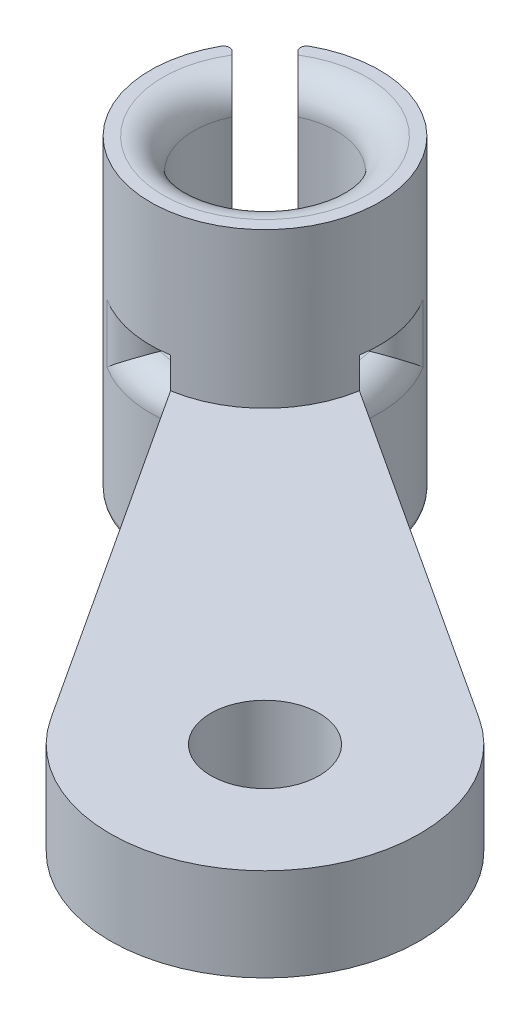
SolidWorks part; units mm, degrees
ref_plane "Front Plane" through (0, 0, 0) normal (0, 0, 1) x (1, 0, 0)
ref_plane "Top Plane" through (0, 0, 0) normal (0, 1, 0) x (1, 0, 0)
ref_plane "Right Plane" through (0, 0, 0) normal (1, 0, 0) x (0, 0, -1)
sketch "Sketch1" plane through (0, 0, 0) normal (0, 1, 0) x (1, 0, 0)
  circle A0 centre (0, 0) radius 2.2
  circle A1 centre (0, 0) radius 3.7
  dimension "D1" = 4.4
  dimension "D2" = 1.5
extrude "Boss-Extrude1" add sketch "Sketch1" along normal blind 5
sketch "Sketch2" plane through (0, 5, 0) normal (0, 1, 0) x (1, 0, 0)
  line L0 (-3.651, 0.6) -> (-2.2204, 0.6)
  line L1 (-3.651, -0.6) -> (-2.2204, -0.6)
  line L2 (0, 0) -> (-4.4135, 0) construction
  line L3 (0.6, 3.651) -> (0.6, 2.2204)
  line L4 (-0.6, 3.651) -> (-0.6, 2.2204)
  line L5 (3.651, -0.6) -> (2.2204, -0.6)
  line L6 (3.651, 0.6) -> (2.2204, 0.6)
  line L7 (-0.6, -3.651) -> (-0.6, -2.2204)
  line L8 (0.6, -3.651) -> (0.6, -2.2204)
  arc A0 (-0.6, 2.2204) -> (-2.2204, 0.6) centre (0, 0) ccw
  arc A1 (-0.6, 3.651) -> (-3.651, 0.6) centre (0, 0) ccw
  circle A2 centre (0, 0) radius 3.7 construction
  circle A3 centre (0, 0) radius 2.3
  arc A4 (-2.2204, -0.6) -> (2.2204, -0.6) centre (0, 0) ccw
  arc A5 (-3.651, -0.6) -> (3.651, -0.6) centre (0, 0) ccw
  arc A6 (3.651, 0.6) -> (0.6, 3.651) centre (0, 0) ccw
  arc A7 (2.2204, 0.6) -> (0.6, 2.2204) centre (0, 0) ccw
  point P22 (0, 0)
  circle M7 centre (0, 0) radius 3.7
  dimension "D2" = 0.6
  dimension "D3" = 0.6
  dimension "D1" = 0.1
  dimension "D4" = 4
extrude "Boss-Extrude2" add sketch "Sketch2" along normal blind 1 contours A0 L4 L0 M7 | A4 L1 L7 M7 | A7 L6 L3 M7 | A4 L8 L5 M7 region at (-2.0496, 5, -2.0496) region at (-2.0496, 5, 2.0496) region at (2.0496, 5, -2.0496) region at (2.0496, 5, 2.0496)
sketch "Sketch3" plane through (0, 6, 0) normal (0, 1, 0) x (1, 0, 0)
  circle A0 centre (0, 0) radius 2.3
  circle A2 centre (0, 0) radius 3.7
extrude "Boss-Extrude3" add sketch "Sketch3" along normal blind 4 contours A2 | A0
sketch "Sketch4" plane through (0, 10, 0) normal (0, 1, 0) x (1, 0, 0)
  line L0 (-3.0923, 2.0317) -> (-1.9928, 0.9321)
  line L1 (-2.0317, 3.0923) -> (-0.9321, 1.9928)
  line L2 (0, 0) -> (-2.6163, 2.6163) construction
  line L11 (0.6, 2.2204) -> (0.6, 3.651)
  line L12 (0.6, 2.2204) -> (0.6, 3.651)
  line L13 (-0.6, 3.651) -> (-0.6, 2.2204)
  line L14 (-0.6, 3.651) -> (-0.6, 2.2204)
  line L21 (-2.2204, 0.6) -> (-3.651, 0.6)
  line L22 (-2.2204, 0.6) -> (-3.651, 0.6)
  line L23 (-3.651, -0.6) -> (-2.2204, -0.6)
  line L24 (-3.651, -0.6) -> (-2.2204, -0.6)
  line L25 (2.2204, -0.6) -> (3.651, -0.6)
  line L26 (2.2204, -0.6) -> (3.651, -0.6)
  line L27 (3.651, 0.6) -> (2.2204, 0.6)
  line L28 (3.651, 0.6) -> (2.2204, 0.6)
  line L29 (0.6, -3.651) -> (0.6, -2.2204)
  line L30 (0.6, -3.651) -> (0.6, -2.2204)
  line L31 (-0.6, -2.2204) -> (-0.6, -3.651)
  line L32 (-0.6, -2.2204) -> (-0.6, -3.651)
  circle A1 centre (0, 0) radius 2.2 construction
  circle A2 centre (0, 0) radius 2.2
  circle A3 centre (0, 0) radius 3.7 construction
  circle A5 centre (0, 0) radius 3.7
  arc A9 (0.6, 3.651) -> (-0.6, 3.651) centre (0, 0) ccw
  arc A15 (0.6, 3.651) -> (-0.6, 3.651) centre (0, 0) ccw
  arc A20 (2.2204, 0.6) -> (0.6, 2.2204) centre (0, 0) ccw
  arc A21 (2.2204, 0.6) -> (0.6, 2.2204) centre (0, 0) ccw
  arc A22 (-0.6, 2.2204) -> (-2.2204, 0.6) centre (0, 0) ccw
  arc A23 (-0.6, 2.2204) -> (-2.2204, 0.6) centre (0, 0) ccw
  arc A24 (-3.651, 0.6) -> (-3.651, -0.6) centre (0, 0) ccw
  arc A25 (-3.651, 0.6) -> (-3.651, -0.6) centre (0, 0) ccw
  arc A26 (-2.2204, -0.6) -> (-0.6, -2.2204) centre (0, 0) ccw
  arc A27 (-2.2204, -0.6) -> (-0.6, -2.2204) centre (0, 0) ccw
  arc A28 (3.651, -0.6) -> (3.651, 0.6) centre (0, 0) ccw
  arc A29 (3.651, -0.6) -> (3.651, 0.6) centre (0, 0) ccw
  arc A30 (0.6, -2.2204) -> (2.2204, -0.6) centre (0, 0) ccw
  arc A31 (0.6, -2.2204) -> (2.2204, -0.6) centre (0, 0) ccw
  arc A32 (-0.6, -3.651) -> (0.6, -3.651) centre (0, 0) ccw
  arc A33 (-0.6, -3.651) -> (0.6, -3.651) centre (0, 0) ccw
  point P2 (-2.6163, 2.6163)
  point P3 (-1.9928, 3.1175)
  point P4 (-3.1175, 1.9928)
  dimension "D2" = 0.75
  dimension "D3" = 0.75
  dimension "D1" = 0
extrude "Cut-Extrude1" cut sketch "Sketch4" against normal through all contours L2 L0 | A2 L2 L0 | L2 A2 L1 A23 | L2 A23 L1 region at (-2.3641, 10, -1.8308) region at (-1.8283, 10, -1.2928) region at (-1.8308, 10, -2.3641) region at (-1.2928, 10, -1.8283)
sketch "Sketch5" plane through (0, 5, 0) normal (0, 1, 0) x (1, 0, 0)
  line L0 (0, 0) -> (12.0208, -12.0208) construction
  line L1 (3.651, -0.6) -> (14.7503, -7.8315)
  line L2 (0.6, -3.651) -> (7.8315, -14.7503)
  line L9 (-1.9928, 0.9321) -> (-2.0678, 1.0071)
  line L15 (-2.2204, 0.6) -> (-3.651, 0.6)
  line L16 (-1.0071, 2.0678) -> (-0.9321, 1.9928)
  line L17 (-1.9928, 0.9321) -> (-2.0678, 1.0071)
  line L24 (-1.0071, 2.0678) -> (-0.9321, 1.9928)
  line L25 (-2.2204, 0.6) -> (-3.651, 0.6)
  line L26 (-3.651, -0.6) -> (-2.2204, -0.6)
  line L27 (-3.651, -0.6) -> (-2.2204, -0.6)
  line L28 (2.2204, -0.6) -> (3.651, -0.6)
  line L29 (2.2204, -0.6) -> (3.651, -0.6)
  line L30 (3.651, 0.6) -> (2.2204, 0.6)
  line L31 (3.651, 0.6) -> (2.2204, 0.6)
  line L32 (0.6, 2.2204) -> (0.6, 3.651)
  line L33 (0.6, 2.2204) -> (0.6, 3.651)
  line L34 (-0.6, 3.651) -> (-0.6, 2.2204)
  line L35 (-0.6, 3.651) -> (-0.6, 2.2204)
  line L36 (-0.6, -2.2204) -> (-0.6, -3.651)
  line L37 (-0.6, -2.2204) -> (-0.6, -3.651)
  line L38 (0.6, -3.651) -> (0.6, -2.2204)
  line L39 (0.6, -3.651) -> (0.6, -2.2204)
  circle A0 centre (12.0208, -12.0208) radius 1.75
  arc A1 (7.8315, -14.7503) -> (14.7503, -7.8315) centre (12.0208, -12.0208) ccw
  arc A3 (-3.0923, 2.0317) -> (-2.0317, 3.0923) centre (0, 0) ccw construction
  arc A4 (-3.0923, 2.0317) -> (-2.0317, 3.0923) centre (0, 0) ccw
  arc A11 (-3.651, 0.6) -> (-3.651, -0.6) centre (0, 0) ccw
  arc A15 (-2.0678, 1.0071) -> (-2.2204, 0.6) centre (0, 0) ccw
  arc A17 (-1.9928, 0.9321) -> (-0.9321, 1.9928) centre (0, 0) ccw
  arc A19 (-3.651, 0.6) -> (-3.651, -0.6) centre (0, 0) ccw
  arc A25 (-1.9928, 0.9321) -> (-0.9321, 1.9928) centre (0, 0) ccw
  arc A26 (-2.2204, -0.6) -> (-0.6, -2.2204) centre (0, 0) ccw
  arc A27 (-2.2204, -0.6) -> (-0.6, -2.2204) centre (0, 0) ccw
  arc A28 (3.651, -0.6) -> (3.651, 0.6) centre (0, 0) ccw
  arc A29 (3.651, -0.6) -> (3.651, 0.6) centre (0, 0) ccw
  arc A30 (2.2204, 0.6) -> (0.6, 2.2204) centre (0, 0) ccw
  arc A31 (2.2204, 0.6) -> (0.6, 2.2204) centre (0, 0) ccw
  arc A32 (0.6, 3.651) -> (-0.6, 3.651) centre (0, 0) ccw
  arc A33 (0.6, 3.651) -> (-0.6, 3.651) centre (0, 0) ccw
  arc A34 (-0.6, -3.651) -> (0.6, -3.651) centre (0, 0) ccw
  arc A35 (-0.6, -3.651) -> (0.6, -3.651) centre (0, 0) ccw
  arc A36 (0.6, -2.2204) -> (2.2204, -0.6) centre (0, 0) ccw
  arc A37 (0.6, -2.2204) -> (2.2204, -0.6) centre (0, 0) ccw
  arc A38 (-2.0678, 1.0071) -> (-2.2204, 0.6) centre (0, 0) ccw
  arc A40 (-0.6, 2.2204) -> (-1.0071, 2.0678) centre (0, 0) ccw
  arc A41 (-0.6, 2.2204) -> (-1.0071, 2.0678) centre (0, 0) ccw
  dimension "D2" = 3.5
  dimension "D3" = 10
  dimension "D1" = 17
  dimension "D4" = 0
extrude "Boss-Extrude4" add sketch "Sketch5" against normal blind 3 contours L2 A1 L1 A0 region at (9.2635, 5, 9.2635)
fillet "Fillet1" radius 0.2 2 edges at (-3.0923, 5, -2.0317) (-2.0317, 5, -3.0923)
fillet "Fillet2" radius 0.9 8 edges at (3.7, 5, 0) (-3.651, 5.5, 0.6) (-3.7, 5, 0) (0, 5, -3.7) (-0.6, 5.5, 3.651) (0, 5, 3.7) (3.651, 5.5, -0.6) (0.6, 5.5, -3.651)
fillet "Fillet3" radius 1 2 edges at (1.5556, 0, 1.5556) (1.6263, 10, 1.6263)
fillet "Fillet4" radius 0.2 9 edges at (-0.9321, 3, -1.9928) (-1.1984, 0.2339, -2.2591) (-1.7605, 0, -2.8212) (-1.9083, 0, -3.0811) (2.6163, 0, 2.6163) (-3.0811, 0, -1.9083) (-2.8212, 0, -1.7605) (-2.1423, 0.4002, -1.0816) (-1.9928, 3, -0.9321)
